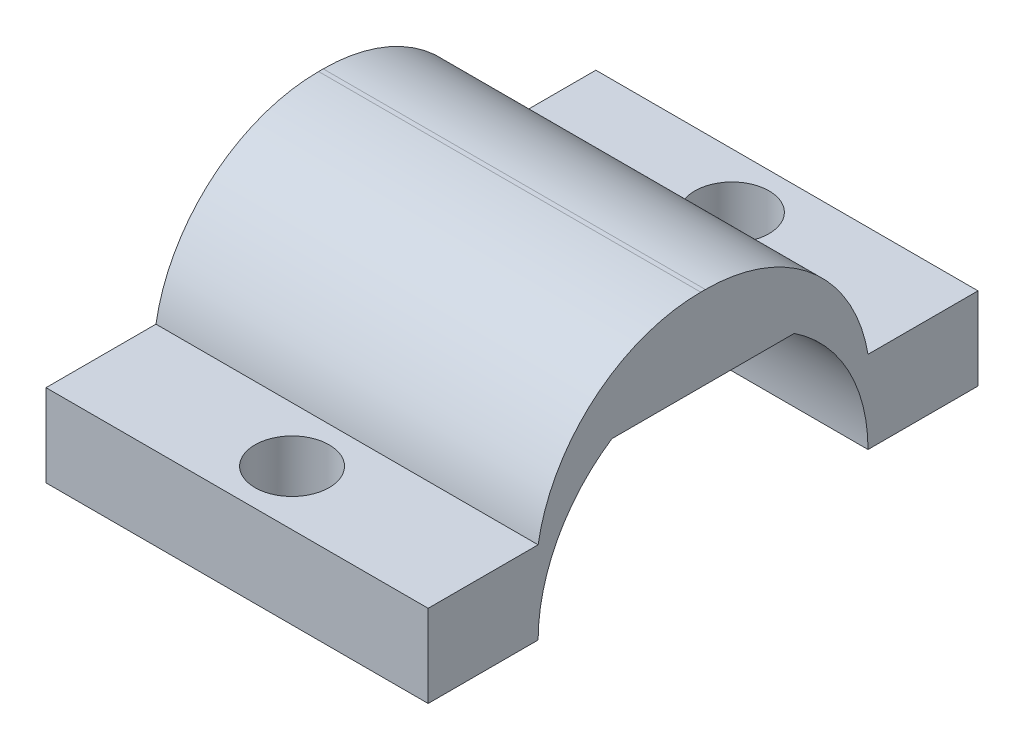
SolidWorks part; units mm, degrees
ref_plane "Plano frontal" through (0, 0, 0) normal (0, 0, 1) x (1, 0, 0)
ref_plane "Plano superior" through (0, 0, 0) normal (0, 1, 0) x (1, 0, 0)
ref_plane "Plano direito" through (0, 0, 0) normal (1, 0, 0) x (0, 0, -1)
sketch "Esboço1" plane through (0, 0, 0) normal (1, 0, 0) x (0, 0, -1)
  line L0 (0, -6) -> (0, -5)
  line L1 (0, 6) -> (0, 5)
  line L2 (-6, 0) -> (6, 0)
  line L3 (-3.3166, 5) -> (3.3166, 5)
  line L4 (-6, 0) -> (-10, 0)
  line L5 (6, 0) -> (10, 0)
  line L6 (-10, 0) -> (-10, 3)
  line L7 (10, 0) -> (10, 3)
  line L8 (-10, 3) -> (-6, 3)
  line L9 (-6, 3) -> (-6, 8)
  line L10 (-6, 8) -> (6, 8)
  line L11 (10, 3) -> (6, 3)
  line L12 (6, 3) -> (6, 8)
  circle A0 centre (0, 0) radius 6
  point P12 (0, 5)
  point P16 (0, 0)
  dimension "D1" = 12
  dimension "D2" = 1
  dimension "D3" = 1
  dimension "D4" = 4
  dimension "D5" = 4
  dimension "D6" = 3
  dimension "D7" = 3
  dimension "D8" = 2
extrude "Ressalto-extrusão1" add sketch "Esboço1" along normal blind 13.9 contours A0 L5 L7 L11 L12 L10 L9 L8 L6 L4 | L1 A0 L3 | L3 A0 L1 region at (0, 5.403, -1.2588) region at (0, 5.9508, 1.7942) region at (0, 5.403, 1.2588)
fillet "Filete1" radius 6 2 edges at (6.95, 8, 6) (6.95, 8, -6)
sketch "Esboço2" plane through (0, 3, 0) normal (0, 1, 0) x (1, 0, 0)
  line L0 (6.95, -6) -> (6.95, -10)
  line L1 (13.9, -6) -> (0, -6) construction
  line L2 (13.9, -10) -> (0, -10) construction
  line L3 (6.95, 6) -> (6.95, 10)
  line L4 (13.9, 6) -> (0, 6) construction
  line L5 (13.9, 10) -> (0, 10) construction
  circle A0 centre (6.95, 8) radius 1.35
  circle A1 centre (6.95, -8) radius 1.35
  dimension "D1" = 2.7
  dimension "D2" = 2.7
extrude "Corte-extrusão1" cut sketch "Esboço2" against normal blind 13.9 contours L3 A0 | L3 A0 | L0 A1 | L0 A1 region at (7.523, 3, 8) region at (6.377, 3, 8) region at (6.377, 3, -8) region at (7.523, 3, -8)
